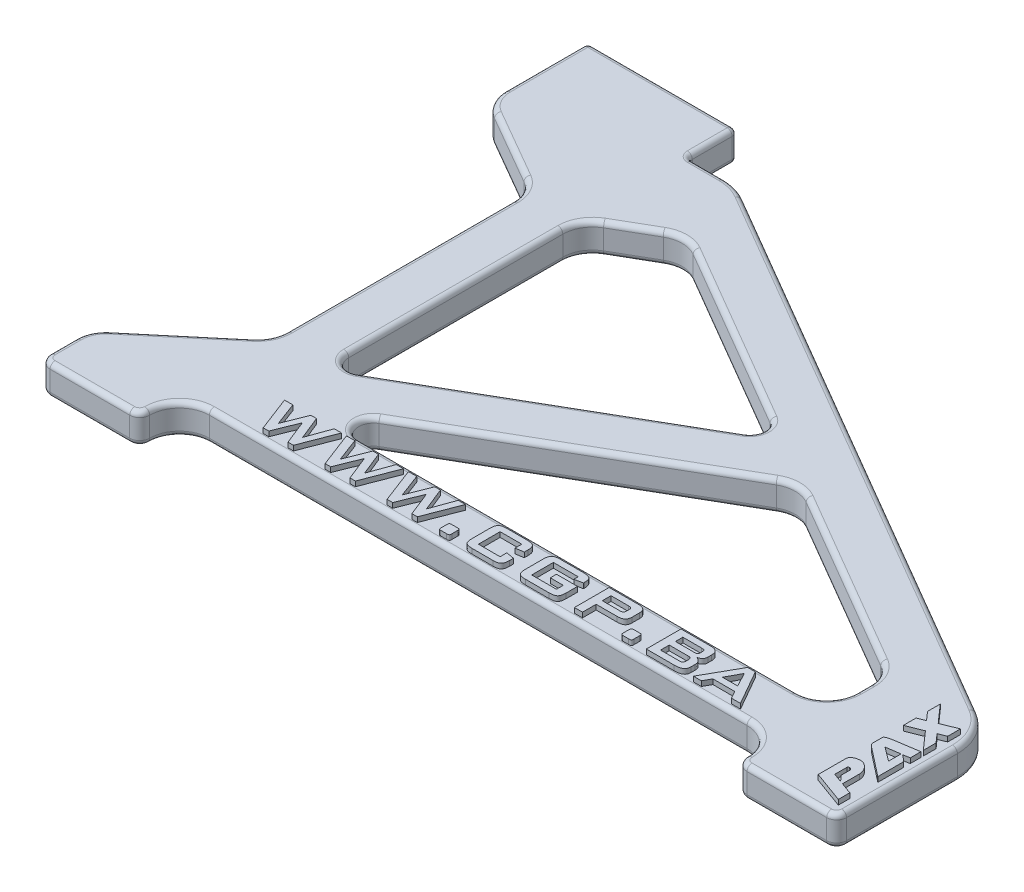
SolidWorks part; units mm, degrees
ref_plane "Front Plane" through (0, 0, 0) normal (0, 0, 1) x (1, 0, 0)
ref_plane "Top Plane" through (0, 0, 0) normal (0, 1, 0) x (1, 0, 0)
ref_plane "Right Plane" through (0, 0, 0) normal (1, 0, 0) x (0, 0, -1)
sketch "Sketch1" plane through (0, 0, 0) normal (0, 1, 0) x (1, 0, 0)
  line L0 (0, 0) -> (0, 5)
  line L1 (0, 5) -> (15, 5)
  line L2 (15, 5) -> (15, 0)
  line L3 (0, 0) -> (0, -50)
  line L4 (0, -50) -> (80, -50)
  line L5 (80, -50) -> (80, -35)
  line L6 (80, -35) -> (20, 0)
  line L7 (20, 0) -> (15, 0)
  dimension "D1" = 5
  dimension "D2" = 15
  dimension "D3" = 50
  dimension "D4" = 80
  dimension "D5" = 15
  dimension "D6" = 5
extrude "Boss-Extrude1" add sketch "Sketch1" along normal blind 3
sketch "Sketch2" plane through (0, 3, 0) normal (0, 1, 0) x (1, 0, 0)
  line L0 (0, -5) -> (8.5, -9.9075)
  line L1 (0, 5) -> (0, -50) construction
  line L2 (10, -12.5056) -> (10, -35.2101)
  line L3 (8.9284, -37.5082) -> (0, -45)
  line L4 (0, -50) -> (80, -50) construction
  line L5 (15, 5) -> (0, 5) construction
  line L6 (0, -5) -> (0, -45)
  line L8 (13, -46) -> (67, -46)
  line L9 (10, -49) -> (10, -54)
  line L10 (10, -54) -> (70, -54)
  line L11 (70, -49) -> (70, -54)
  line L12 (10, -46) -> (70, -54) construction
  line L13 (10, -54) -> (70, -46) construction
  line L14 (15, -12.5056) -> (15, -34.0109)
  line L16 (16.5, -9.9075) -> (20.3, -7.7135)
  line L17 (77.4806, -39.3189) -> (17.4806, -4.3189)
  line L18 (41.834, -18.525) -> (23.3116, -7.7203)
  line L19 (17.25, -35.31) -> (41.8282, -21.1197)
  line L21 (22.2426, -38.201) -> (47.5331, -23.5995)
  line L22 (22.9926, -41) -> (67, -41)
  line L24 (17.5, -40.9391) -> (46.5666, -24.1575) construction
  line L25 (50.5447, -23.6063) -> (68.5116, -34.087)
  line L26 (10, -41) -> (70, -41) construction
  line L28 (70, -38) -> (70, -36.6783)
  line L29 (15, -10.7735) -> (15, -36.609) construction
  line L30 (15, -36.609) -> (44.0666, -19.8274) construction
  line L31 (10, -10.7735) -> (10, -36.609) construction
  line L32 (10, -46) -> (70, -46) construction
  arc A0 (22.2426, -38.201) -> (22.9926, -41) centre (22.9926, -39.5) ccw
  arc A1 (15, -34.0109) -> (17.25, -35.31) centre (16.5, -34.0109) ccw
  arc A2 (41.8282, -21.1197) -> (41.834, -18.525) centre (41.0782, -19.8207) ccw
  arc A5 (67, -41) -> (70, -38) centre (67, -38) ccw
  arc A6 (68.5116, -34.087) -> (70, -36.6783) centre (67, -36.6783) cw
  arc A7 (47.5331, -23.5995) -> (50.5447, -23.6063) centre (49.0331, -26.1976) cw
  arc A8 (20.3, -7.7135) -> (23.3116, -7.7203) centre (21.8, -10.3116) cw
  arc A9 (15, -12.5056) -> (16.5, -9.9075) centre (18, -12.5056) cw
  arc A10 (10, -35.2101) -> (8.9284, -37.5082) centre (7, -35.2101) cw
  arc A11 (8.5, -9.9075) -> (10, -12.5056) centre (7, -12.5056) cw
  arc A12 (13, -46) -> (10, -49) centre (13, -49) ccw
  arc A13 (67, -46) -> (70, -49) centre (67, -49) cw
  point P10 (40, -50)
  point P38 (0, -45)
  point P41 (0, -5)
  point P57 (10, -36.609)
  dimension "D12" = 1.5
  dimension "D13" = 3
  dimension "D14" = 3
  dimension "D1" = 10
  dimension "D2" = 5
  dimension "D3" = 10
  dimension "D4" = 60
  dimension "D5" = 50
  dimension "D6" = 8
  dimension "D7" = 5
  dimension "D9" = 120
  dimension "D10" = 5
  dimension "D8" = 5
  dimension "D11" = 5
extrude "Cut-Extrude1" cut sketch "Sketch2" against normal blind 3
fillet "Fillet1" radius 3 2 edges at (0, 1.5, 45) (0, 1.5, 5)
fillet "Fillet2" radius 1 4 edges at (80, 1.5, 50) (70, 1.5, 50) (10, 1.5, 50) (0, 1.5, 50)
fillet "Fillet3" radius 5 2 edges at (20, 1.5, 0) (80, 1.5, 35)
sketch "Sketch3" plane through (0, 3, 0) normal (0, 1, 0) x (1, 0, 0)
  line L2 (79, -49) -> (79, -37.8719)
  line L3 (79, -49) -> (79, -37.8719) construction
  text T0 "WWW.CGP.BA" font "BankGothic Md BT" height in points 13
  text T1 "pax" font "Airstrike" height in points 12
  dimension "D1" = 1
extrude "Boss-Extrude2" add sketch "Sketch3" along normal blind 0.5
fillet "Fillet4" radius 0.5 85 edges at (0, 3, -0.866) (0.4019, 3, 4.7679) (5, 3, 7.8868) (9.5981, 3, 11.0056) (10, 3, 23.8578) (9.7189, 3, 36.4779) (5, 3, 40.8045) (0.2811, 3, 45.1311) (0, 3, 47.6995) (0.2929, 3, 49.7071) (5, 3, 50) (9.7071, 3, 49.7071) (10.8787, 3, 46.8787) (40, 3, 46) (69.1213, 3, 46.8787) (70.2929, 3, 49.7071) (75, 3, 50) (79.7071, 3, 49.7071) (80, 3, 43.4359) (79.3357, 3, 35.3815) (16.8241, 3, 0) (19.9532, 3, 0.1733) (0, 0, -0.866) (0.4019, 0, 4.7679) (5, 0, 7.8868) (9.5981, 0, 11.0056) (10, 0, 23.8578) (9.7189, 0, 36.4779) (5, 0, 40.8045) (0.2811, 0, 45.1311) (0, 0, 47.6995) (0.2929, 0, 49.7071) (5, 0, 50) (9.7071, 0, 49.7071) (10.8787, 0, 46.8787) (40, 0, 46) (69.1213, 0, 46.8787) (70.2929, 0, 49.7071) (75, 0, 50) (79.7071, 0, 49.7071) (80, 0, 43.4359) (79.3357, 0, 35.3815) (16.8241, 0, 0) (19.9532, 0, 0.1733) (15.4019, 0, 11.0056) (18.4, 0, 8.8105) (21.8067, 0, 7.3116) (32.5728, 0, 13.1227) (42.5782, 0, 19.8241) (29.5391, 0, 28.2148) (15.75, 0, 35.31) (15.4019, 3, 11.0056) (18.4, 3, 8.8105) (21.8067, 3, 7.3116) (32.5728, 3, 13.1227) (42.5782, 3, 19.8241) (29.5391, 3, 28.2148) (15.75, 3, 35.31) (34.8879, 0, 30.9002) (49.0398, 0, 23.1976) (59.5282, 0, 28.8466) (69.6014, 0, 35.1841) (70, 0, 37.3391) (69.1213, 0, 40.1213) (44.9963, 0, 41) (34.8879, 3, 30.9002) (49.0398, 3, 23.1976) (59.5282, 3, 28.8466) (69.6014, 3, 35.1841) (70, 3, 37.3391) (69.1213, 3, 40.1213) (44.9963, 3, 41) (7.5, 3, -5) (0, 1.5, -5) (7.5, 0, -5) (15, 1.5, 0) (15, 3, -2.5) (15, 1.5, -5) (15, 0, -2.5) (49.3435, 3, 17.117) (49.3435, 0, 17.117) (15, 0, 23.2582) (15, 3, 23.2582) (21.5438, 0, 39.8882) (21.5438, 3, 39.8882)
